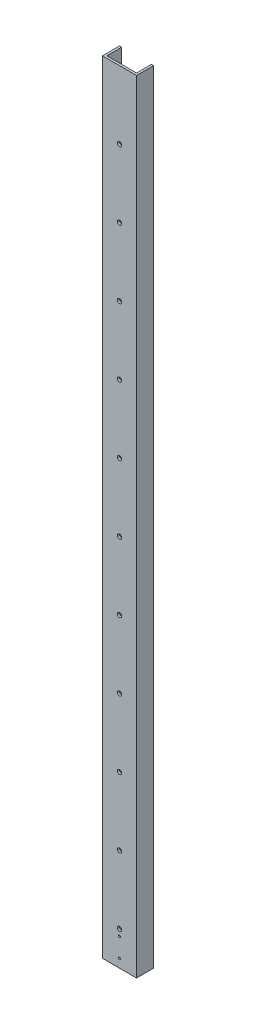
SolidWorks part; units mm, degrees
ref_plane "Front" through (0, 0, 0) normal (0, 0, 1) x (1, 0, 0)
ref_plane "Top" through (0, 0, 0) normal (0, 1, 0) x (1, 0, 0)
ref_plane "Right" through (0, 0, 0) normal (1, 0, 0) x (0, 0, -1)
sketch "Sketch1" plane through (0, 0, 0) normal (0, 1, 0) x (1, 0, 0)
  line L0 (3.175, 3.175) -> (3.175, 25.4)
  line L1 (0, 0) -> (50.8, 0)
  line L2 (0, 0) -> (0, 25.4)
  line L4 (50.8, 0) -> (50.8, 25.4)
  line L5 (3.175, 3.175) -> (47.625, 3.175)
  line L6 (47.625, 3.175) -> (47.625, 25.4)
  line L7 (0, 25.4) -> (3.175, 25.4)
  line L8 (50.8, 25.4) -> (47.625, 25.4)
  dimension "D1" = 25.4
  dimension "D2" = 50.8
  dimension "D3" = 3.175
extrude "Boss-Extrude1" add sketch "Sketch1" along normal blind 1168.4
sketch "Sketch2" plane through (0, 0, 0) normal (0, 0, 1) x (1, 0, 0)
  line L0 (25.4, 0) -> (25.4, 50.8) construction
  line L1 (0, 0) -> (50.8, 0) construction
  circle A0 centre (25.4, 50.8) radius 3.175
  circle A1 centre (25.4, 152.4) radius 3.175
  circle A2 centre (25.4, 254) radius 3.175
  circle A3 centre (25.4, 355.6) radius 3.175
  circle A4 centre (25.4, 457.2) radius 3.175
  circle A5 centre (25.4, 558.8) radius 3.175
  circle A6 centre (25.4, 660.4) radius 3.175
  circle A7 centre (25.4, 762) radius 3.175
  circle A8 centre (25.4, 863.6) radius 3.175
  circle A9 centre (25.4, 965.2) radius 3.175
  circle A10 centre (25.4, 1066.8) radius 3.175
  dimension "D2" = 6.35
  dimension "D1" = 50.8
  dimension "D3" = 11
extrude "Cut-Extrude1" cut sketch "Sketch2" against normal up to next
sketch "Sketch4" plane through (0, 0, 0) normal (0, 0, 1) x (1, 0, 0)
  line L0 (25.4, 41.275) -> (50.8, 41.275) construction
  line L1 (50.8, 1168.4) -> (50.8, 0) construction
  line L2 (25.4, 41.275) -> (0, 41.275) construction
  line L3 (0, 1168.4) -> (0, 0) construction
  line L4 (25.4, 41.275) -> (25.4, 12.7) construction
  line L5 (25.4, 12.7) -> (25.4, 0) construction
  line L6 (0, 0) -> (50.8, 0) construction
  circle A1 centre (25.4, 41.275) radius 1.5875
  circle A3 centre (25.4, 12.7) radius 1.5875
  dimension "D1" = 28.575
  dimension "D2" = 12.7
extrude "Cut-Extrude2" cut sketch "Sketch4" against normal up to next
